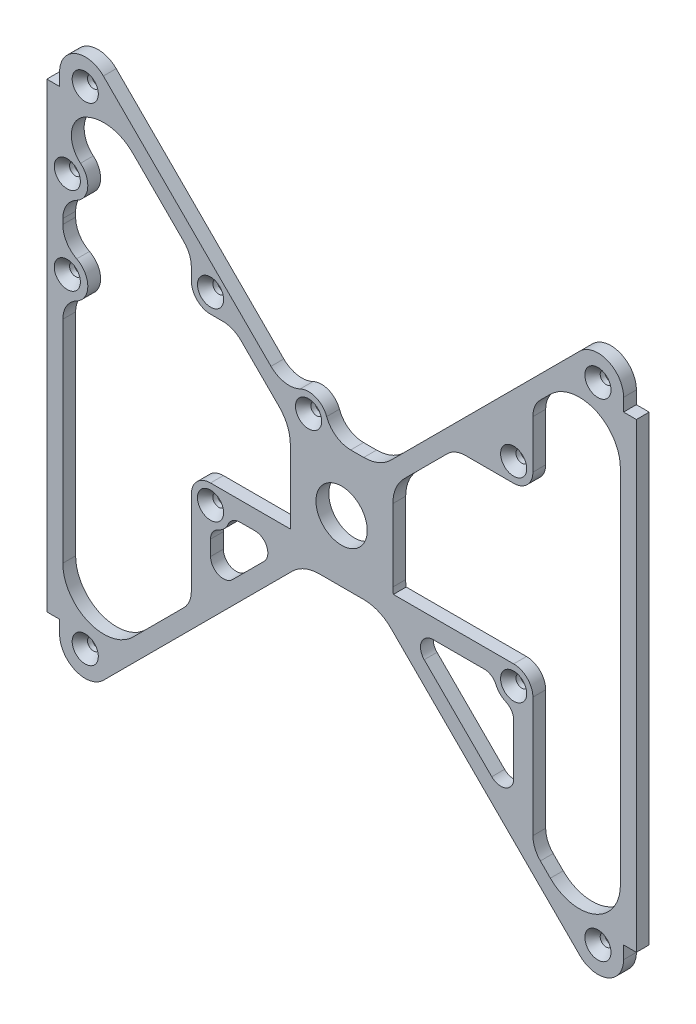
SolidWorks part; units mm, degrees
material "6061-T6 (SS)"
ref_plane "Front Plane" through (0, 0, 0) normal (0, 0, 1) x (1, 0, 0)
ref_plane "Top Plane" through (0, 0, 0) normal (0, 1, 0) x (1, 0, 0)
ref_plane "Right Plane" through (0, 0, 0) normal (1, 0, 0) x (0, 0, -1)
sketch "Sketch1" plane through (0, 0, 0) normal (0, 0, 1) x (1, 0, 0)
  line L0 (0, 0) -> (0, 73.025) construction
  line L1 (0, 0) -> (73.025, 0) construction
  line L2 (73.025, 73.025) -> (73.025, 0) construction
  line L3 (9.4347, 15.24) -> (0, 15.24)
  line L4 (12.7, 12.8926) -> (12.7, 0)
  line L5 (9.4347, 15.24) -> (59.0099, 64.8151)
  line L6 (12.7, 12.8926) -> (51.712, 51.9046)
  line L7 (69.0563, 44.7204) -> (69.0563, 0)
  line L8 (0, 73.025) -> (73.025, 73.025) construction
  line L9 (73.025, 57.15) -> (73.025, 0)
  line L10 (69.85, 60.325) -> (69.85, 57.15)
  line L11 (0, 0) -> (12.7, 0)
  line L12 (0, 15.24) -> (0, 0)
  line L13 (69.0563, 0) -> (73.025, 0)
  line L26 (69.85, 57.15) -> (73.025, 57.15)
  arc A1 (69.85, 60.325) -> (59.0099, 64.8151) centre (63.5, 60.325) ccw
  arc A2 (51.712, 51.9046) -> (69.0563, 44.7204) centre (58.8963, 44.7204) cw
  point P51 (12, 0)
  dimension "D11" = 6.35
  dimension "D5" = 10.16
  dimension "D3" = 12.7
  dimension "D6" = 3.9688
  dimension "D7" = 73.025
  dimension "D10" = 12.7
  dimension "D2" = 73.025
  dimension "D4" = 15.24
  dimension "D9" = 9.525
  dimension "D12" = 135
  dimension "D14" = 3.9688
  dimension "D8" = 15.875
extrude "Boss-Extrude1" add sketch "Sketch1" along normal blind 3.175
sketch "LOCATES-SCREW" plane through (0, 0, 3.175) normal (0, 0, 1) x (1, 0, 0)
  point P0 (63.5, 60.325)
hole_wizard "CSK for #4 Flat Head Machine Screw1" positions "Sketch10" profile "Sketch11" countersink size "#4" standard "ANSI Inch" end condition through all
sketch "Sketch10" plane through (0, 0, 3.175) normal (0, 0, 1) x (1, 0, 0)
  point P0 (63.5, 60.325)
sketch "Sketch11" plane through (63.5, 60.325, 3.175) normal (1, 0, 0) x (0, -1, 0)
  line L0 (0, 0) -> (0, 3.175)
  line L1 (0, 3.175) -> (1.4732, 3.175)
  line L2 (1.4732, 3.175) -> (1.4732, 2.0307)
  line L3 (1.4732, 2.0307) -> (3.2385, 0)
  line L5 (3.2385, 0) -> (0, 0)
  line L6 (-1.4732, 2.0307) -> (-3.2385, 0) construction
  line L11 (0, -6.35) -> (0, 107.95) construction
  dimension "Thru Hole Dia." = 2.9464
  dimension "Thru Hole Depth" = 3.175
  dimension "Near C'Sink Dia." = 6.477
  dimension "Near C'Sink Angle" = 82
mirror "Mirror1" about plane through (0, 0, 0) normal (0, 1, 0) of "CSK for #4 Flat Head Machine Screw1", "Boss-Extrude1"
mirror "Mirror2" about plane through (0, 0, 0) normal (1, 0, 0) of "Mirror1", "Boss-Extrude1", "CSK for #4 Flat Head Machine Screw1"
chamfer "COUNTERSINK" [suppressed] distance 1.27 angle 45
fillet "INTERNAL-SHARPS" radius 9.525 8 edges at (9.4347, 15.24, 1.5875) (-9.4347, 15.24, 1.5875) (12.7, -12.8926, 1.5875) (12.7, 12.8926, 1.5875) (9.4347, -15.24, 1.5875) (-9.4347, -15.24, 1.5875) (-12.7, -12.8926, 1.5875) (-12.7, 12.8926, 1.5875)
sketch "Sketch5" plane through (0, 0, 0) normal (0, 0, 1) x (1, 0, 0)
  line L0 (15.4898, 15.6824) -> (51.712, 51.9046) construction
  line L1 (69.0563, 44.7204) -> (69.0563, -44.7204) construction
  line L2 (73.025, 0) -> (54, 0) construction
  line L3 (69.0563, 12.7) -> (57.785, 12.7)
  line L4 (55.245, -10.7499) -> (55.245, 10.7499)
  line L5 (73.025, -57.15) -> (73.025, 57.15) construction
  line L6 (32.9011, 33.0937) -> (35.1462, 35.3388)
  line L7 (55.245, 10.7499) -> (32.9011, 33.0937)
  line L8 (57.785, 12.7) -> (35.1462, 35.3388)
  line L9 (69.0563, 12.7) -> (69.0563, -12.7)
  line L10 (69.0563, -12.7) -> (57.785, -12.7)
  line L11 (57.785, -12.7) -> (35.1462, -35.3388)
  line L12 (55.245, -10.7499) -> (32.9011, -33.0937)
  line L13 (32.9011, -33.0937) -> (35.1462, -35.3388)
  circle A0 centre (58.7375, 7.9375) radius 1.65 construction
  circle A1 centre (68.2625, 7.9375) radius 1.65 construction
  circle A2 centre (68.2625, -7.9375) radius 1.65 construction
  circle A3 centre (58.7375, -7.9375) radius 1.65 construction
  dimension "D1" = 3.3
  dimension "D2" = 12.7
  dimension "D3" = 15.24
  dimension "D4" = 9.525
  dimension "D5" = 15.875
  dimension "D6" = 4.7625
  dimension "D7" = 3.175
  dimension "D8" = 17.78
extrude "BRAKE-MOUNT" [suppressed] add sketch "Sketch5" along normal blind 3.175
sketch "PROJECTED-FROM-SKETCH-5" plane through (0, 0, 3.175) normal (0, 0, 1) x (1, 0, 0)
  circle A0 centre (58.7375, 7.9375) radius 1.65 construction
  circle A1 centre (58.7375, 7.9375) radius 1.65
  circle A2 centre (68.2625, 7.9375) radius 1.65 construction
  circle A3 centre (68.2625, -7.9375) radius 1.65 construction
  circle A4 centre (58.7375, -7.9375) radius 1.65 construction
  circle A5 centre (68.2625, 7.9375) radius 1.65
  circle A6 centre (68.2625, -7.9375) radius 1.65
  circle A7 centre (58.7375, -7.9375) radius 1.65
extrude "Cut-Extrude1" [suppressed] cut sketch "PROJECTED-FROM-SKETCH-5" against normal through all
fillet "Fillet1" [suppressed] radius 6.35
sketch "Sketch6" plane through (0, 0, 0) normal (0, 0, -1) x (-1, 0, 0)
  circle A0 centre (0, 0) radius 6.35
  dimension "D1" = 12.7
sketch "Sketch13" plane through (0, 0, 0) normal (0, 0, 1) x (1, 0, 0)
  line L0 (-73.025, 57.15) -> (-73.025, -57.15) construction
  line L1 (-73.025, 44.45) -> (-73.025, 12.7)
  line L2 (-73.025, 12.7) -> (-67.945, 12.7)
  line L3 (-73.025, 44.45) -> (-67.945, 44.45)
  line L4 (-69.0563, -44.7204) -> (-69.0563, 44.7204) construction
  line L5 (-69.0562, 22.737) -> (-69.0563, 34.413)
  arc A0 (-69.0563, 34.413) -> (-67.945, 44.45) centre (-67.945, 39.37) ccw
  arc A1 (-67.945, 12.7) -> (-69.0562, 22.737) centre (-67.945, 17.78) ccw
  circle A3 centre (-63.5, 60.325) radius 1.4732 construction
  point P6 (-73.025, 28.575)
  point P7 (-67.2288, 19.9693)
  point P16 (0, 0)
  dimension "D1" = 31.75
  dimension "D2" = 21.59
  dimension "D3" = 31.75
  dimension "D4" = 5.08
extrude "IMU-MOUNTING" add sketch "Sketch13" along normal blind 3.175
hole_wizard "IMU-MOUNTING-HOLES" positions "Sketch14" profile "Sketch15" countersink size "#4" standard "ANSI Inch" end condition through all
sketch "Sketch14" plane through (0, 0, 3.175) normal (0, 0, 1) x (1, 0, 0)
  arc A0 (-67.945, 12.7) -> (-69.0563, 22.737) centre (-67.945, 17.78) ccw construction
  point P1 (-67.945, 17.78)
  point P7 (-67.945, 39.37)
  dimension "D1" = 21.59
sketch "Sketch15" plane through (-67.945, 17.78, 3.175) normal (1, 0, 0) x (0, -1, 0)
  line L0 (0, 0) -> (0, 3.175)
  line L1 (0, 3.175) -> (1.4732, 3.175)
  line L2 (1.4732, 3.175) -> (1.4732, 2.0307)
  line L3 (1.4732, 2.0307) -> (3.2385, 0)
  line L5 (3.2385, 0) -> (0, 0)
  line L6 (-1.4732, 2.0307) -> (-3.2385, 0) construction
  line L11 (0, -6.35) -> (0, 107.95) construction
  dimension "Thru Hole Dia." = 2.9464
  dimension "Thru Hole Depth" = 3.175
  dimension "Near C'Sink Dia." = 6.477
  dimension "Near C'Sink Angle" = 82
fillet "IMU-TOOLING-RADIUS" radius 6.35 4 edges at (-69.0563, 44.45, 1.5875) (-69.0563, 12.7, 1.5875) (-69.0562, 22.737, 1.5875) (-69.0563, 34.413, 1.5875)
hole_wizard "CSK for #4 Flat Head Machine Screw2" [suppressed] positions "3DSketch2" profile "Sketch17" countersink size "#4" standard "ANSI Inch"
sketch3d "3DSketch2"
  point P0 (58.7375, -7.9375, 3.175)
  point P3 (58.7375, 7.9375, 3.175)
  point P6 (68.2625, 7.9375, 3.175)
  point P9 (68.2625, -7.9375, 3.175)
sketch "Sketch17" plane through (58.7375, -7.9375, 3.175) normal (1, 0, 0) x (0, -1, 0)
  line L0 (0, 0) -> (0, 3.175)
  line L1 (0, 3.175) -> (1.4732, 3.175)
  line L2 (1.4732, 3.175) -> (1.4732, 1.5925)
  line L3 (1.4732, 1.5925) -> (2.8575, 0)
  line L5 (2.8575, 0) -> (0, 0)
  line L6 (-1.4732, 1.5925) -> (-2.8575, 0) construction
  line L11 (0, -6.35) -> (0, 107.95) construction
  dimension "Thru Hole Dia." = 2.9464
  dimension "Thru Hole Depth" = 3.175
  dimension "Near C'Sink Dia." = 5.715
  dimension "Near C'Sink Angle" = 82
sketch "Sketch18" plane through (0, 0, 0) normal (0, 0, -1) x (-1, 0, 0)
  line L0 (-42.6212, 33.02) -> (-42.6212, -15.24) construction
  line L1 (32.4612, -13.97) -> (32.4612, 31.75) construction
  line L2 (32.4612, 8.89) -> (-42.6212, 8.89) construction
  line L3 (15.4898, -15.6824) -> (51.712, -51.9046) construction
  line L4 (32.4612, -32.6538) -> (37.2237, -37.4163)
  line L5 (32.4612, -9.2075) -> (9.0149, -9.2075)
  line L6 (37.2237, -13.97) -> (37.2237, -37.4163)
  line L7 (32.4612, -18.7325) -> (32.4612, -32.6538)
  line L8 (27.6987, -13.97) -> (13.7774, -13.97)
  line L9 (9.0149, -9.2075) -> (13.7774, -13.97)
  line L10 (32.4612, 26.9875) -> (26.7949, 26.9875)
  line L11 (37.2237, 31.75) -> (37.2237, 37.4163)
  line L13 (0, 0) -> (0, -3.8457) construction
  line L14 (15.4898, 15.6824) -> (51.712, 51.9046) construction
  line L15 (26.7949, 26.9875) -> (37.2237, 37.4163)
  line L16 (-5.08, 8.89) -> (-5.08, 27.7139) construction
  line L17 (-42.6212, -10.4775) -> (-10.2849, -10.4775)
  line L18 (-47.3837, -15.24) -> (-47.3837, -47.5763)
  line L19 (-42.6212, -20.0025) -> (-42.6212, -42.8138)
  line L20 (-37.8587, -15.24) -> (-15.0474, -15.24)
  line L21 (-15.4898, -15.6824) -> (-51.712, -51.9046) construction
  line L22 (-42.6212, -42.8138) -> (-47.3837, -47.5763)
  line L23 (-10.2849, -10.4775) -> (-15.0474, -15.24)
  line L24 (-42.6212, 28.2575) -> (-28.0649, 28.2575)
  line L26 (-47.3837, 33.02) -> (-47.3837, 47.5763)
  line L28 (-12.7, 12.8926) -> (-51.712, 51.9046) construction
  line L30 (-28.0649, 28.2575) -> (-47.3837, 47.5763)
  line L31 (-12.7, -8.9472) -> (-12.7, 8.9472) construction
  line L32 (-12.7, -8.9472) -> (-12.7, 8.9472)
  circle A0 centre (32.4612, -13.97) radius 1.5875 construction
  circle A1 centre (32.4612, 31.75) radius 1.5875 construction
  circle A2 centre (-42.6212, -15.24) radius 1.5875 construction
  circle A3 centre (-42.6212, 33.02) radius 1.5875 construction
  circle A4 centre (8.1788, 17.78) radius 1.5875 construction
  arc A5 (32.4612, -9.2075) -> (37.2237, -13.97) centre (32.4612, -13.97) cw
  arc A6 (27.6987, -13.97) -> (32.4612, -18.7325) centre (32.4612, -13.97) ccw
  arc A7 (32.4612, 26.9875) -> (37.2237, 31.75) centre (32.4612, 31.75) ccw
  arc A9 (-42.6212, -10.4775) -> (-47.3837, -15.24) centre (-42.6212, -15.24) ccw
  arc A10 (-37.8587, -15.24) -> (-42.6212, -20.0025) centre (-42.6212, -15.24) cw
  arc A11 (-42.6212, 28.2575) -> (-47.3837, 33.02) centre (-42.6212, 33.02) cw
  circle A13 centre (8.1788, 17.78) radius 4.7625
  arc A14 (-15.4898, -15.6824) -> (-12.7, -8.9472) centre (-22.225, -8.9472) ccw construction
  arc A15 (-15.4898, -15.6824) -> (-12.7, -8.9472) centre (-22.225, -8.9472) ccw
  point P0 (-42.6212, -15.24)
  point P1 (-42.6212, 33.02)
  point P2 (8.1788, 17.78)
  point P3 (32.4612, -13.97)
  point P4 (32.4612, 31.75)
  dimension "D6" = 3.175
  dimension "D7" = 4.7625
  dimension "D9" = 4.7625
  dimension "D12" = 4.7625
  dimension "D17" = 4.7625
  dimension "D18" = 4.7625
  dimension "D23" = 4.7625
  dimension "D27" = 9.525
  dimension "D1" = 45.72
  dimension "D2" = 48.26
  dimension "D5" = 75.0824
  dimension "D8" = 45
  dimension "D10" = 4.7625
  dimension "D11" = 4.7625
  dimension "D19" = 4.7625
  dimension "D20" = 4.7625
  dimension "D21" = 45
  dimension "D28" = 8.89
  dimension "D3" = 15.24
  dimension "D4" = 50.8
  dimension "D13" = 5.08
extrude "MCU-MOUNTING-RIBS" add sketch "Sketch18" against normal up to surface (3.175 mm away) contours L5 L9 L8 A6 L7 L4 L6 A5 | A0 | A2 | L18 L22 L19 A10 L20 L23 L17 A9 | L15 L11 A7 L10 | A1 | A3 | L26 A11 L24 L30 | A13 | A4
fillet "TOOLING-RADIUS" radius 6.35 8 edges at (-37.2237, 37.4163, 1.5875) (-37.2237, -37.4163, 1.5875) (-26.7949, 26.9875, 1.5875) (28.0649, 28.2575, 1.5875) (47.3837, 47.5763, 1.5875) (47.3837, -47.5763, 1.5875) (-12.8586, 18.6638, 1.5875) (-4.1502, 15.24, 1.5875)
fillet "TOOLING-RADIUS-SMALL" radius 3.175 8 edges at (42.6212, -20.0025, 1.5875) (37.8587, -15.24, 1.5875) (42.6212, -42.8138, 1.5875) (-32.4612, -18.7325, 1.5875) (-27.6987, -13.97, 1.5875) (-32.4612, -32.6538, 1.5875) (-14.132, -13.97, 1.5875) (15.0747, -15.24, 1.5875)
extrude "MATERIAL-REMOVAL" cut sketch "Sketch6" against normal through all contours A0
hole_wizard "MCU-MOUNTING-HOLES" positions "Sketch19" profile "Sketch20" countersink size "#4" standard "ANSI Inch" end condition through all
sketch "Sketch19" plane through (0, 0, 3.175) normal (0, 0, 1) x (1, 0, 0)
  point P0 (-32.4612, -13.97)
  point P3 (-32.4612, 31.75)
  point P6 (42.6212, 33.02)
  point P9 (42.6212, -15.24)
  point P12 (-8.1788, 17.78)
sketch "Sketch20" plane through (-32.4612, -13.97, 3.175) normal (1, 0, 0) x (0, -1, 0)
  line L0 (0, 0) -> (0, 3.175)
  line L1 (0, 3.175) -> (1.4732, 3.175)
  line L2 (1.4732, 3.175) -> (1.4732, 2.0307)
  line L3 (1.4732, 2.0307) -> (3.2385, 0)
  line L5 (3.2385, 0) -> (0, 0)
  line L6 (-1.4732, 2.0307) -> (-3.2385, 0) construction
  line L11 (0, -6.35) -> (0, 107.95) construction
  dimension "Thru Hole Dia." = 2.9464
  dimension "Thru Hole Depth" = 3.175
  dimension "Near C'Sink Dia." = 6.477
  dimension "Near C'Sink Angle" = 82
equation "\"D14@Sketch1\"=\"D6@Sketch1\""
equation "\"D9@Sketch18\"=\"D7@Sketch18\""
equation "\"D10@Sketch18\"=\"D7@Sketch18\""
equation "\"D11@Sketch18\"=\"D7@Sketch18\""
equation "\"D18@Sketch18\"=\"D17@Sketch18\""
equation "\"D19@Sketch18\"=\"D17@Sketch18\""
equation "\"D20@Sketch18\"=\"D17@Sketch18\""
